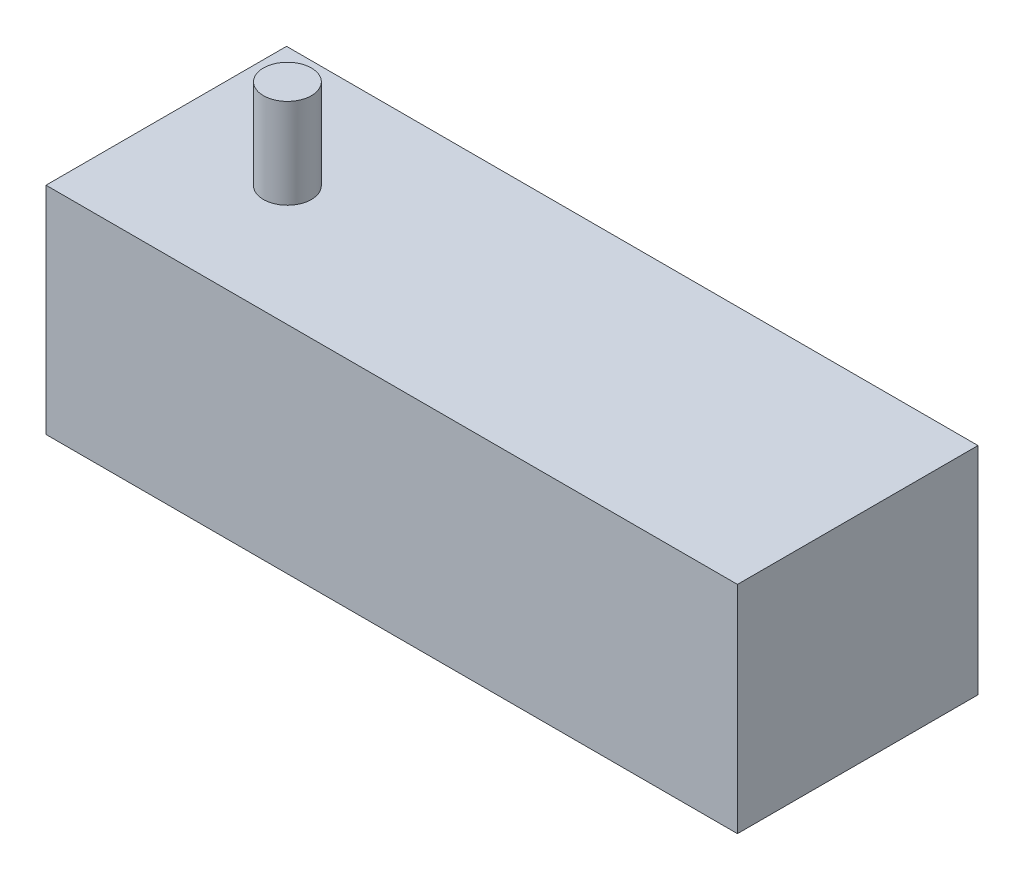
SolidWorks part; units mm, degrees
ref_plane "Front Plane" through (0, 0, 0) normal (0, 0, 1) x (1, 0, 0)
ref_plane "Top Plane" through (0, 0, 0) normal (0, 1, 0) x (1, 0, 0)
ref_plane "Right Plane" through (0, 0, 0) normal (1, 0, 0) x (0, 0, -1)
sketch "Sketch1" plane through (0, 0, 0) normal (0, 1, 0) x (1, 0, 0)
  line L1 (0, 0) -> (115.3, 0)
  line L2 (0, 0) -> (0, 40.11)
  line L3 (0, 40.11) -> (115.3, 40.11)
  line L4 (115.3, 0) -> (115.3, 40.11)
extrude "Boss-Extrude1" add sketch "Sketch1" along normal blind 36
sketch "Sketch2" plane through (0, 36, 0) normal (0, 1, 0) x (1, 0, 0)
  circle A0 centre (20.2, 20.055) radius 4
  point P2 (0, 0)
extrude "Boss-Extrude2" add sketch "Sketch2" along normal blind 15
